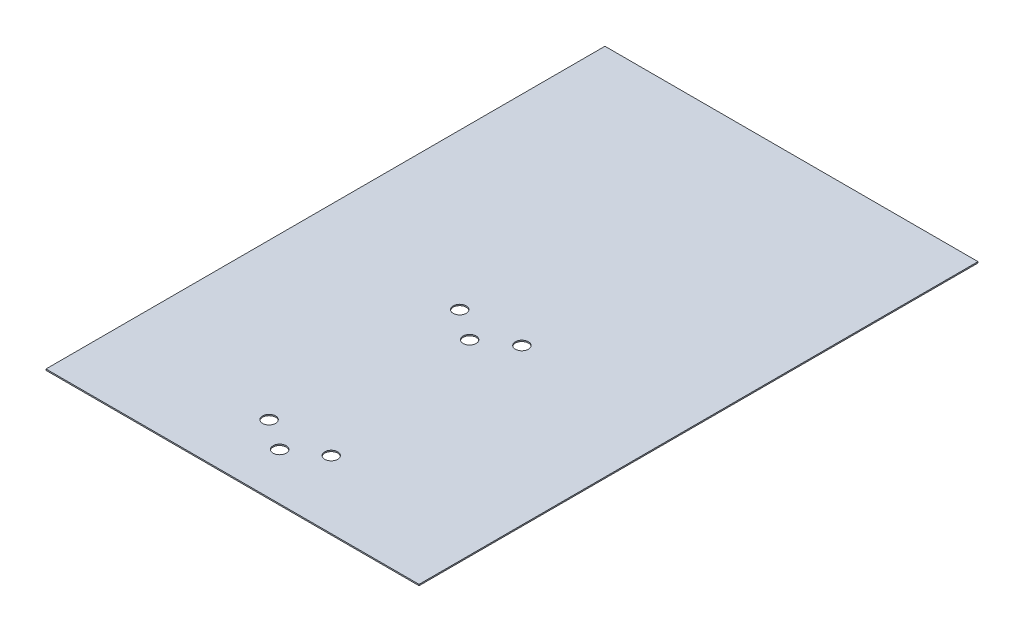
SolidWorks part; units mm, degrees
ref_plane "Front Plane" through (0, 0, 0) normal (0, 0, 1) x (1, 0, 0)
ref_plane "Top Plane" through (0, 0, 0) normal (0, 1, 0) x (1, 0, 0)
ref_plane "Right Plane" through (0, 0, 0) normal (1, 0, 0) x (0, 0, -1)
sketch "Sketch1" plane through (0, 0, 0) normal (0, 1, 0) x (1, 0, 0)
  line L1 (76.2, 0) -> (0, 0)
  line L2 (76.2, 0) -> (76.2, 114.173)
  line L3 (76.2, 114.173) -> (0, 114.173)
  line L4 (0, 0) -> (0, 114.173)
extrude "Boss-Extrude1" add sketch "Sketch1" along normal blind 0.254
sketch "Sketch2" plane through (0, 0.254, 0) normal (0, 1, 0) x (1, 0, 0)
  circle A0 centre (31.75, 13.8176) radius 1.3335
  circle A1 centre (44.45, 13.8176) radius 1.3335
  circle A2 centre (38.1, 9.6266) radius 1.3335
  circle A3 centre (31.75, 52.7558) radius 1.3335
  circle A4 centre (44.45, 52.7558) radius 1.3335
  circle A5 centre (38.1, 48.4378) radius 1.3335
extrude "Cut-Extrude1" cut sketch "Sketch2" against normal blind 2.54
